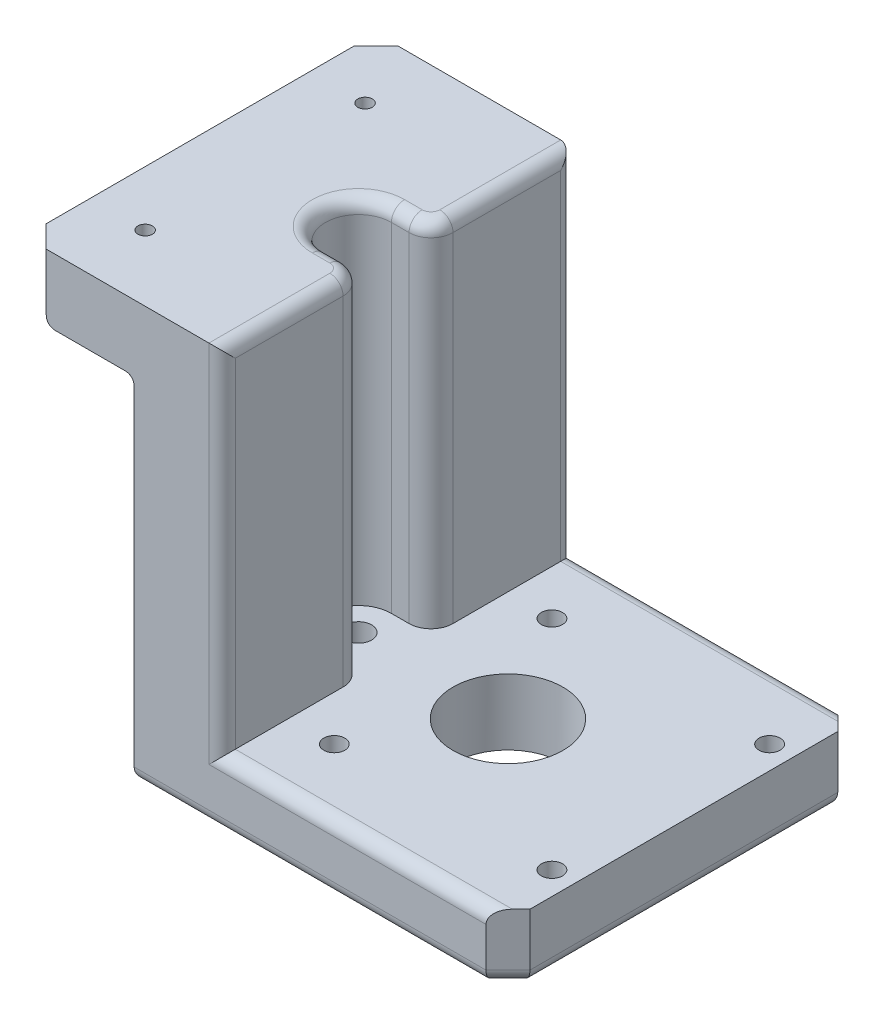
SolidWorks part; units mm, degrees
material "PLA"
ref_plane "Front Plane" through (0, 0, 0) normal (0, 0, 1) x (1, 0, 0)
ref_plane "Top Plane" through (0, 0, 0) normal (0, 1, 0) x (1, 0, 0)
ref_plane "Right Plane" through (0, 0, 0) normal (1, 0, 0) x (0, 0, -1)
sketch "Sketch1" plane through (0, 0, 0) normal (0, 1, 0) x (1, 0, 0)
  line L1 (0, 0) -> (90, 0)
  line L2 (0, 0) -> (0, 80)
  line L3 (0, 80) -> (90, 80)
  line L4 (90, 0) -> (90, 80)
  dimension "D1" = 80
  dimension "D2" = 90
extrude "Boss-Extrude1" add sketch "Sketch1" along normal blind 15
sketch "Sketch2" plane through (0, 0, 0) normal (0, -1, 0) x (1, 0, 0)
  line L0 (90, -40) -> (16, -40) construction
  line L1 (90, 0) -> (90, -80) construction
  circle A0 centre (16, -40) radius 7
  dimension "D2" = 14
  dimension "D1" = 74
extrude "Cut-Extrude1" cut sketch "Sketch2" against normal blind 5
chamfer "Chamfer1" distance 5 angle 45 4 edges at (90, 7.5, -80) (90, 7.5, 0) (0, 7.5, -80) (0, 7.5, 0)
sketch "Sketch3" plane through (0, 15, 0) normal (0, 1, 0) x (1, 0, 0)
  line L0 (60, 65) -> (60, 15) construction
  line L1 (85, 65) -> (35, 65) construction
  line L2 (35, 15) -> (85, 15) construction
  line L3 (35, 40) -> (85, 40) construction
  line L4 (35, 65) -> (35, 15) construction
  line L5 (85, 15) -> (85, 65) construction
  circle A0 centre (35.2513, 64.7487) radius 2.4
  circle A1 centre (84.7487, 64.7487) radius 2.4
  circle A2 centre (84.7487, 15.2513) radius 2.4
  circle A3 centre (35.2513, 15.2513) radius 2.4
  circle A4 centre (50, 40) radius 12.5
  circle A5 centre (16, 40) radius 4.25
  dimension "D1" = 4.8
  dimension "D2" = 8.5
  dimension "D3" = 25
extrude "Cut-Extrude2" cut sketch "Sketch3" against normal blind 20
sketch "Sketch4" plane through (0, 15, 0) normal (0, 1, 0) x (1, 0, 0)
  circle A0 centre (16, 40) radius 6.2313
  circle A1 centre (16, 40) radius 3
  dimension "D1" = 6
extrude "Boss-Extrude2" add sketch "Sketch4" against normal up to surface (10 mm away) up to face at (16, 5, -44.25)
sketch "Sketch5" plane through (0, 15, 0) normal (0, 1, 0) x (1, 0, 0)
  line L0 (5, 0) -> (85, 0) construction
  line L1 (0, 5) -> (5, 0) construction
  line L2 (0, 75) -> (0, 5) construction
  line L3 (5, 80) -> (0, 75) construction
  line L4 (85, 80) -> (5, 80) construction
  line L5 (5, 0) -> (25, 0)
  line L6 (0, 5) -> (5, 0)
  line L7 (0, 75) -> (0, 5)
  line L8 (5, 80) -> (0, 75)
  line L9 (25, 80) -> (5, 80)
  line L10 (25, 80) -> (25, 52.5)
  line L11 (16, 47.5) -> (20, 47.5)
  line L12 (16, 32.5) -> (20, 32.5)
  line L13 (25, 27.5) -> (25, 0)
  arc A0 (16, 47.5) -> (16, 32.5) centre (16, 40) ccw
  arc A1 (25, 52.5) -> (20, 47.5) centre (20, 52.5) cw
  arc A2 (25, 27.5) -> (20, 32.5) centre (20, 27.5) ccw
  point P18 (25, 32.5)
  dimension "D2" = 15
  dimension "D3" = 5
  dimension "D1" = 25
extrude "Boss-Extrude3" add sketch "Sketch5" along normal blind 60
sketch "Sketch6" plane through (0, 75, 0) normal (0, 1, 0) x (1, 0, 0)
  line L0 (5, 80) -> (-20, 80)
  line L1 (-20, 80) -> (-20, 0)
  line L2 (-20, 0) -> (5, 0)
  line L4 (-7.5, 80) -> (-7.5, 0) construction
  line L15 (0, 5) -> (5, 0)
  line L16 (5, 0) -> (25, 0)
  line L17 (25, 0) -> (25, 27.5)
  line L18 (20, 32.5) -> (16, 32.5)
  line L19 (16, 47.5) -> (20, 47.5)
  line L20 (25, 52.5) -> (25, 80)
  line L21 (25, 80) -> (5, 80)
  line L22 (5, 80) -> (0, 75)
  line L23 (0, 75) -> (0, 5)
  line L25 (5, 0) -> (25, 0)
  line L26 (25, 0) -> (25, 27.5)
  line L27 (20, 32.5) -> (16, 32.5)
  line L28 (16, 47.5) -> (20, 47.5)
  line L29 (25, 52.5) -> (25, 80)
  line L30 (25, 80) -> (5, 80)
  circle A0 centre (-7.5, 65) radius 1.65
  circle A1 centre (-7.5, 15) radius 1.65
  arc A5 (25, 27.5) -> (20, 32.5) centre (20, 27.5) ccw
  arc A6 (16, 47.5) -> (16, 32.5) centre (16, 40) ccw
  arc A7 (20, 47.5) -> (25, 52.5) centre (20, 52.5) ccw
  arc A8 (25, 27.5) -> (20, 32.5) centre (20, 27.5) ccw
  arc A9 (16, 47.5) -> (16, 32.5) centre (16, 40) ccw
  arc A10 (20, 47.5) -> (25, 52.5) centre (20, 52.5) ccw
  dimension "D2" = 3.3
  dimension "D1" = 25
  dimension "D3" = 50
  dimension "D4" = 15
  dimension "D5" = 0
extrude "Boss-Extrude4" add sketch "Sketch6" along normal blind 20
chamfer "Chamfer2" distance 5 angle 45 4 edges at (-20, 85, 0) (-7.5, 75, 0) (-20, 85, -80) (-7.5, 75, -80)
fillet "Fillet1" radius 3 25 edges at (25, 95, -13.75) (23.5355, 95, -31.0355) (18, 95, -32.5) (8.5, 95, -40) (18, 95, -47.5) (23.5355, 95, -48.9645) (87.5, 0, -2.5) (90, 0, -40) (87.5, 0, -77.5) (45, 0, -80) (2.5, 0, -77.5) (0, 0, -40) (2.5, 0, -2.5) (45, 0, 0) (55, 15, 0) (25, 55, 0) (55, 15, -80) (25, 55, -80) (25, 95, -66.25) (2.5, 77.5, -2.5) (2.5, 77.5, -77.5) (0, 75, -40) (-17.5, 77.5, -77.5) (-17.5, 77.5, -2.5) (-20, 75, -40)
